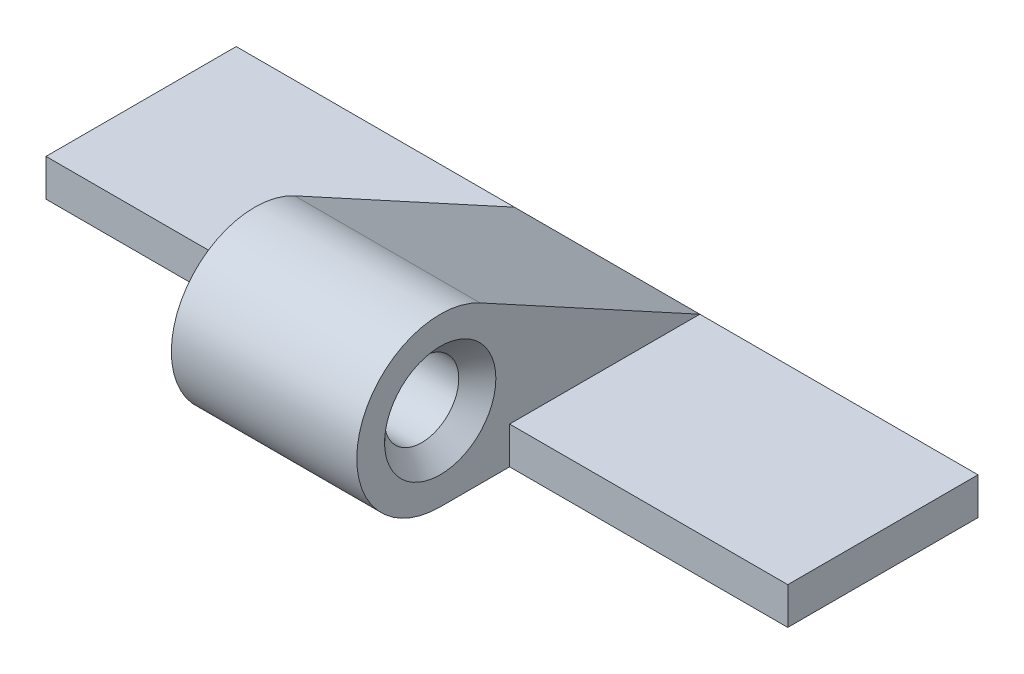
SolidWorks part; units mm, degrees
ref_plane "Ebene vorne" through (0, 0, 0) normal (0, 0, 1) x (1, 0, 0)
ref_plane "Ebene oben" through (0, 0, 0) normal (0, 1, 0) x (1, 0, 0)
ref_plane "Ebene rechts" through (0, 0, 0) normal (1, 0, 0) x (0, 0, -1)
sketch "Skizze2" plane through (0, 0, 0) normal (0, 1, 0) x (1, 0, 0)
  line L1 (-7.5, 3.5) -> (7.5, 3.5)
  line L2 (-7.5, 3.5) -> (-7.5, -3.5)
  line L3 (-7.5, -3.5) -> (7.5, -3.5)
  line L4 (7.5, 3.5) -> (7.5, -3.5)
  line L5 (-7.5, 3.5) -> (7.5, -3.5) construction
  line L6 (-7.5, -3.5) -> (7.5, 3.5) construction
  point P0 (0, 0)
  dimension "D1" = 15
  dimension "D2" = 7
extrude "Aufsatz-Linear austragen1" add sketch "Skizze2" along normal blind 1
sketch "Skizze3" plane through (7.5, 0, 0) normal (1, 0, 0) x (0, 0, -1)
  circle A0 centre (-3.5, 2.25) radius 2.25
  circle A1 centre (-3.5, 2.25) radius 1
  dimension "D1" = 2
  dimension "D2" = 4.5
extrude "Aufsatz-Linear austragen2" add sketch "Skizze3" against normal up to surface (15 mm away) up to face at (-7.5, 0.5, 0)
ref_plane "Tangential Ebene" through (0, 0, 1.25) normal (0, 0, -1) x (-1, 0, 0)
sketch "Skizze5" plane through (7.5, 0, 0) normal (1, 0, 0) x (0, 0, -1)
  line L0 (-1.6292, 1) -> (-1.6292, 0)
  line L1 (-1.6292, 0) -> (-3.5, 0)
  line L3 (3.5, 1) -> (-1.6292, 1)
  line L4 (-3.5, 0) -> (3.5, 0)
  line L5 (3.5, 0) -> (3.5, 1)
  line L6 (3.5, 1) -> (-1.6292, 1) construction
  line L7 (-3.5, 0) -> (3.5, 0) construction
  line L8 (3.5, 0) -> (3.5, 1) construction
  arc A1 (-1.6292, 1) -> (-3.5, 0) centre (-3.5, 2.25) ccw
  arc A2 (-1.6292, 1) -> (-3.5, 0) centre (-3.5, 2.25) ccw
  dimension "D1" = 0
extrude "Schnitt-Linear austragen1" cut sketch "Skizze5" against normal blind 5
pattern_linear "Lineares Muster1" count 2 spacing 10 along (-1, 0, 0) of "Schnitt-Linear austragen1"
ref_plane "Spiegelebene" through (0, 0, 0) normal (1, 0, 0) x (0, 0, -1)
sketch "Skizze7" plane through (7.5, 0, 0) normal (1, 0, 0) x (0, 0, -1)
  line L1 (3.5, 1) -> (-1.6292, 1)
  line L2 (3.5, 1) -> (3.5, 0)
  line L3 (3.5, 0) -> (-1.6292, 0)
  line L4 (-1.6292, 1) -> (-1.6292, 0)
extrude "Verbreiterung" add sketch "Skizze7" along normal blind 2.5
mirror "Spiegeln1" about plane through (0, 0, 0) normal (1, 0, 0) of "Verbreiterung"
ref_axis "Achse1" through (-2.5, 2.25, 3.5) along (1, 0, 0)
chamfer "Fase1" distance 0.5 angle 45 2 edges at (-2.5, 2.25, 2.5) (2.5, 2.25, 2.5)
sketch "Skizze9" plane through (2.5, 0, 0) normal (1, 0, 0) x (0, 0, -1)
  line L0 (-1.6292, 1) -> (3.5, 1)
  line L1 (3.5, 1) -> (-2.4239, 4.226)
  line L2 (-2.4239, 4.226) -> (-1.6292, 1)
  arc A0 (-1.6292, 1) -> (-3.5, 0) centre (-3.5, 2.25) ccw construction
  point P7 (0, 0)
extrude "Aufsatz-Linear austragen3" add sketch "Skizze9" against normal up to surface (5 mm away) from surface up to face at (-2.5, 2.25, 2) starting at face at (2.5, 2.25, 2)
